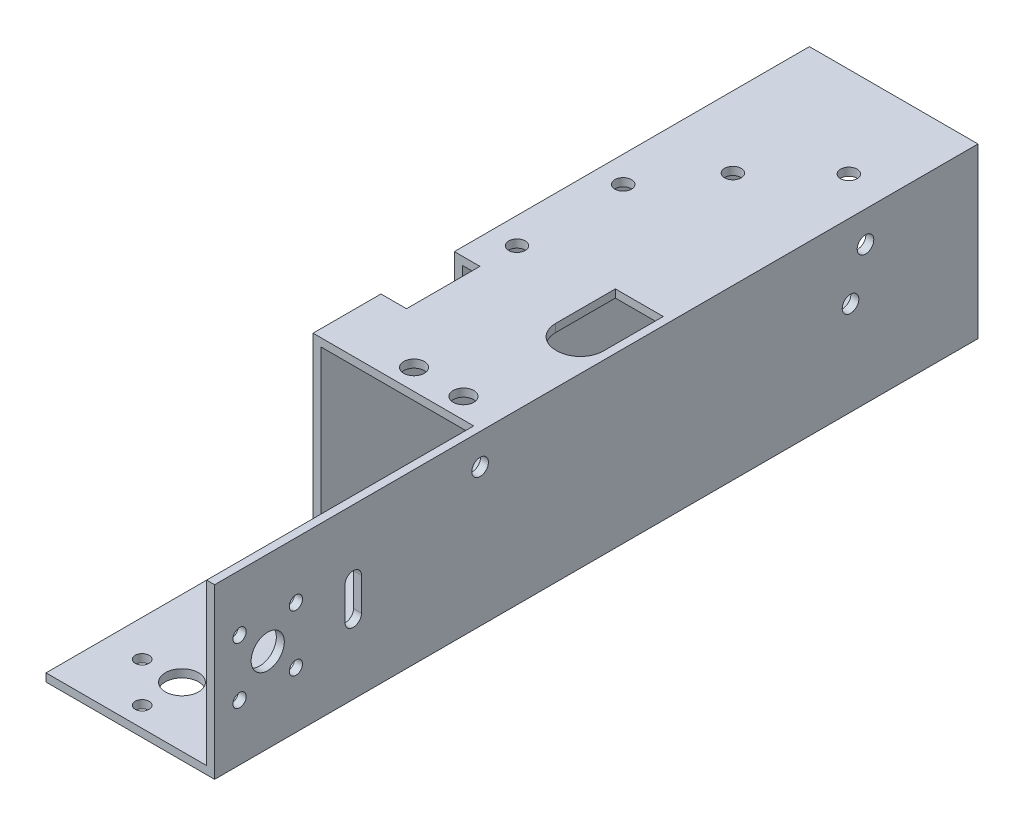
SolidWorks part; units mm, degrees
note: The reader was unsure of these and kept them because the rebuilt part matched: shared geometry of "Sketch3<3>".
material "6063-O"
ref_plane "Front Plane" through (0, 0, 0) normal (0, 0, 1) x (1, 0, 0)
ref_plane "Top Plane" through (0, 0, 0) normal (0, 1, 0) x (1, 0, 0)
ref_plane "Right Plane" through (0, 0, 0) normal (1, 0, 0) x (0, 0, -1)
sketch "Sketch1" plane through (0, 0, 0) normal (0, 0, 1) x (1, 0, 0)
  line L0 (52.1684, 33.1696) -> (52.1684, 10.1696)
  line L1 (50.9684, 34.3696) -> (76.3684, 34.3696)
  line L2 (50.9684, 34.3696) -> (50.9684, 8.9696)
  line L3 (50.9684, 8.9696) -> (76.3684, 8.9696)
  line L4 (76.3684, 34.3696) -> (76.3684, 8.9696)
  line L5 (50.9684, 34.3696) -> (76.3684, 8.9696) construction
  line L6 (50.9684, 8.9696) -> (76.3684, 34.3696) construction
  line L7 (52.1684, 10.1696) -> (75.1684, 10.1696)
  line L8 (75.1684, 33.1696) -> (75.1684, 10.1696)
  line L9 (52.1684, 33.1696) -> (75.1684, 33.1696)
  point P0 (63.6684, 21.6696)
  dimension "D1" = 25.4
  dimension "D2" = 1.2
extrude "Boss-Extrude1" add sketch "Sketch1" along normal blind 115
sketch "Sketch2" plane through (50.9684, 0, 0) normal (-1, 0, 0) x (0, 0, 1)
  line L0 (115, 34.3696) -> (115, 8.9696) construction
  line L1 (115, 37.4513) -> (74.7682, 37.4513)
  line L2 (115, 37.4513) -> (115, 10.1696)
  line L3 (115, 10.1696) -> (74.7682, 10.1696)
  line L4 (74.7682, 37.4513) -> (74.7682, 10.1696)
extrude "Cut-Extrude1" cut sketch "Sketch2" against normal up to vertex
sketch "Sketch5" plane through (76.3684, 0, 0) normal (1, 0, 0) x (0, 0, -1)
  line L0 (-115, 8.9696) -> (-115, 34.3696) construction
  line L1 (-111.2426, 17.4269) -> (-102.7574, 17.4269) construction
  line L2 (-111.2426, 17.4269) -> (-111.2426, 25.9122) construction
  line L3 (-111.2426, 25.9122) -> (-102.7574, 25.9122) construction
  line L4 (-102.7574, 17.4269) -> (-102.7574, 25.9122) construction
  line L5 (-111.2426, 17.4269) -> (-102.7574, 25.9122) construction
  line L6 (-111.2426, 25.9122) -> (-102.7574, 17.4269) construction
  line L7 (-107, 21.6696) -> (-115, 21.6696) construction
  line L8 (0, 8.9696) -> (0, 34.3696) construction
  line L13 (-94.1148, 19.6047) -> (-94.1148, 24.5207) construction
  line L14 (-95.3563, 19.6047) -> (-95.3563, 24.5207)
  line L15 (-92.8734, 19.6047) -> (-92.8734, 24.5207)
  circle A0 centre (-102.7574, 25.9122) radius 1
  circle A1 centre (-111.2426, 25.9122) radius 1
  circle A2 centre (-111.2426, 17.4269) radius 1
  circle A3 centre (-102.7574, 17.4269) radius 1
  circle A4 centre (-107, 21.6696) radius 2.5
  circle A5 centre (-16.95, 29.7378) radius 1.25
  circle A6 centre (-75, 29.7378) radius 1.25
  arc A7 (-95.3563, 19.6047) -> (-92.8734, 19.6047) centre (-94.1148, 19.6047) ccw
  arc A8 (-92.8734, 24.5207) -> (-95.3563, 24.5207) centre (-94.1148, 24.5207) ccw
  circle A9 centre (-19.2042, 23.1178) radius 1.25
  circle A11 centre (-19.2042, 23.1178) radius 1.55 construction
  point P0 (-107, 21.6696)
  point P26 (-94.1148, 22.0627)
  dimension "D2" = 2
  dimension "D3" = 5
  dimension "D5" = 2.5
  dimension "D7" = 2.5
  dimension "D1" = 12
  dimension "D4" = 8
  dimension "D6" = 58.05
  dimension "D8" = 75
extrude "Cut-Extrude4" cut sketch "Sketch5" against normal blind 10
sketch "Sketch3" plane through (0, 8.9696, 0) normal (0, -1, 0) x (1, 0, 0)
  line L0 (54.9184, 32) -> (54.9184, 48) construction
  line L1 (62.4399, 99.9898) -> (56.4399, 105.9898) construction
  line L2 (62.4399, 99.9898) -> (68.4399, 105.9898) construction
  line L3 (68.4399, 105.9898) -> (62.4399, 111.9898) construction
  line L4 (56.4399, 105.9898) -> (62.4399, 111.9898) construction
  line L5 (62.4399, 99.9898) -> (62.4399, 111.9898) construction
  line L6 (68.4399, 105.9898) -> (56.4399, 105.9898) construction
  line L7 (66.9072, 93.1009) -> (71.3096, 97.9628) construction
  line L8 (65.7859, 94.1163) -> (70.1882, 98.9781)
  line L9 (68.0285, 92.0856) -> (72.4309, 96.9475)
  line L10 (50.9684, 0) -> (76.3684, 0) construction
  circle A0 centre (54.9184, 32) radius 1.25
  circle A1 centre (54.9184, 48) radius 1.25
  circle A2 centre (56.4399, 105.9898) radius 1.05
  circle A3 centre (62.4399, 111.9898) radius 1.05
  circle A4 centre (68.4399, 105.9898) radius 1.05
  circle A5 centre (62.4399, 99.9898) radius 1.05
  circle A6 centre (62.4399, 105.9898) radius 2.5
  arc A7 (65.7859, 94.1163) -> (68.0285, 92.0856) centre (66.9072, 93.1009) ccw
  arc A8 (72.4309, 96.9475) -> (70.1882, 98.9781) centre (71.3096, 97.9628) ccw
  point P6 (62.4399, 105.9898)
  point P11 (69.1084, 95.5319)
  dimension "D1" = 5
  dimension "D2" = 2.1
  dimension "D3" = 2.5
  dimension "D4" = 16
  dimension "D5" = 12
  dimension "D6" = 2.75
  dimension "D7" = 32
extrude "Cut-Extrude2" cut sketch "Sketch3" against normal up to next
sketch "Sketch6" plane through (0, 8.9696, 0) normal (0, -1, 0) x (-1, 0, 0)
  circle A0 centre (-70.4055, -82.5) radius 1.6
  circle A1 centre (-56.0742, -82.5) radius 1.6
  circle A4 centre (-56.0742, -82.5) radius 1.25 construction
  circle A5 centre (-70.4055, -82.5) radius 1.25 construction
  circle A8 centre (-61.7063, -18.4542) radius 1.25
  circle A9 centre (-61.7063, -18.4542) radius 1.55 construction
  dimension "D1" = 3.2
  dimension "D2" = 2.5
extrude "Cut-Extrude5" cut sketch "Sketch6" against normal blind 8
sketch "Sketch9" plane through (76.3684, 0, 0) normal (1, 0, 0) x (0, 0, -1)
  line L0 (-24.4544, 21.6696) -> (0, 21.6696) construction
  line L6 (0, 8.9696) -> (0, 34.3696) construction
extrude "Cut-Extrude9" cut sketch "Sketch3<3>" against normal through all contours A0 | A1
sketch "Sketch3<3>" plane through (0, 8.9696, 0) normal (0, -1, 0) x (1, 0, 0) same geometry as "Sketch3"
sketch "Sketch10" plane through (0, 34.3696, 0) normal (0, 1, 0) x (1, 0, 0)
  line L0 (75.1684, -74.7682) -> (75.1684, -115) construction
  line L1 (67.9598, -58.709) -> (75.1684, -58.709)
  line L2 (67.9598, -58.709) -> (67.9598, -46.2183)
  line L3 (67.9598, -46.2183) -> (75.1684, -46.2183)
  line L4 (75.1684, -58.709) -> (75.1684, -46.2183)
  line L5 (50.9684, -74.7682) -> (50.9684, 0) construction
  line L6 (54.8197, -64.5389) -> (50.9684, -64.5389)
  line L7 (54.8197, -64.5389) -> (54.8197, -53.4813)
  line L8 (54.8197, -53.4813) -> (50.9684, -53.4813)
  line L9 (50.9684, -64.5389) -> (50.9684, -53.4813)
  circle A0 centre (63.0382, -71.6248) radius 1.55
  circle A1 centre (70.5439, -71.6858) radius 1.55
  circle A4 centre (63.0382, -71.6248) radius 1.25 construction
  circle A5 centre (70.5439, -71.6858) radius 1.25 construction
  circle A7 centre (61.7063, -22.2621) radius 1.25
  circle A8 centre (61.7063, -22.2621) radius 1.5 construction
  circle A9 centre (70.5439, -13.6358) radius 1.25
  dimension "D1" = 3.1
  dimension "D2" = 2.5
  dimension "D3" = 2.5
extrude "Cut-Extrude10" cut sketch "Sketch10" against normal blind 5
fillet "Fillet1" radius 3.5 2 edges at (75.1684, 33.7696, 58.709) (67.9598, 33.7696, 58.709)
sketch "Sketch11" plane through (50.9684, 0, 0) normal (-1, 0, 0) x (0, 0, 1)
  circle A0 centre (22.2621, 23.1178) radius 1.25
  circle A1 centre (22.2621, 23.1178) radius 1.5 construction
  dimension "D1" = 2.5
extrude "Cut-Extrude11" cut sketch "Sketch11" against normal blind 8
